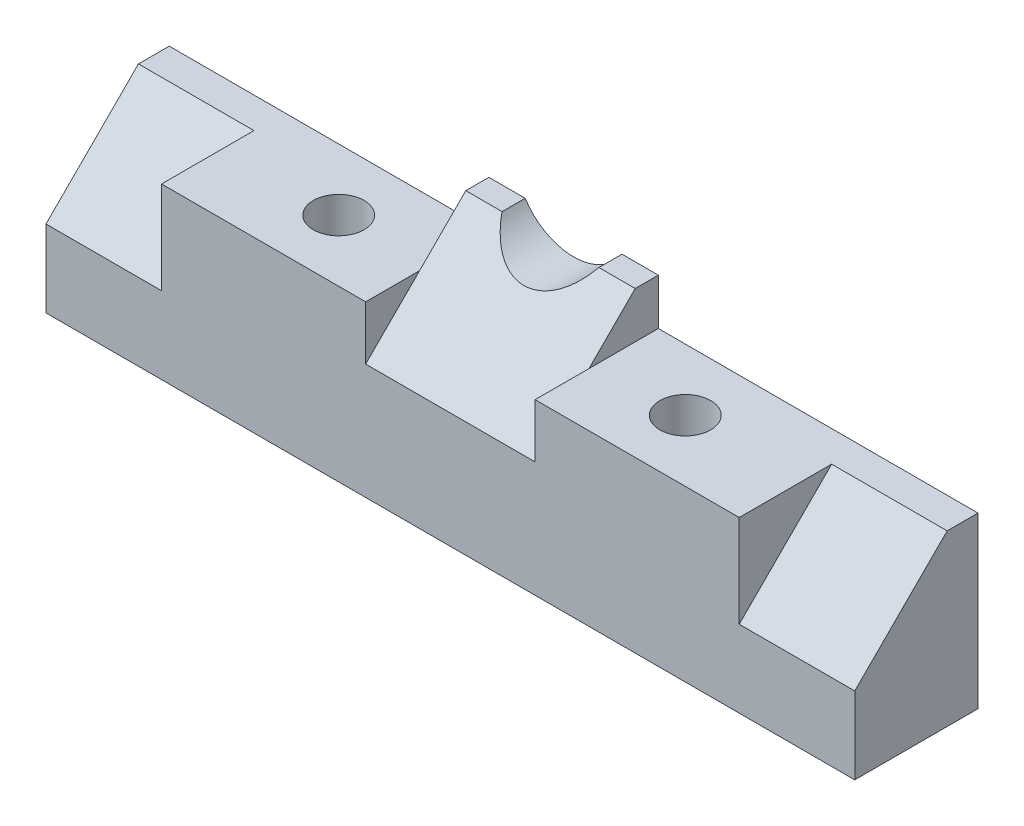
SolidWorks part; units mm, degrees
ref_plane "Alzado" through (0, 0, 0) normal (0, 0, 1) x (1, 0, 0)
ref_plane "Planta" through (0, 0, 0) normal (0, 1, 0) x (1, 0, 0)
ref_plane "Vista lateral" through (0, 0, 0) normal (1, 0, 0) x (0, 0, -1)
sketch "Croquis1" plane through (0, 0, 0) normal (0, 0, 1) x (1, 0, 0)
  line L1 (0, 0) -> (105, 0)
  line L2 (0, 0) -> (0, 22)
  line L3 (0, 22) -> (105, 22)
  line L4 (105, 0) -> (105, 22)
  dimension "D1" = 105
  dimension "D2" = 22
extrude "Saliente-Extruir1" add sketch "Croquis1" along normal blind 16
sketch "Croquis2" plane through (105, 0, 0) normal (1, 0, 0) x (0, 0, -1)
  line L2 (-16, 22) -> (0, 22) construction
  line L4 (-16, 0) -> (-16, 22) construction
  line L8 (-16, 10) -> (-16, 22)
  line L9 (-16, 22) -> (-4, 22)
  line L10 (-16, 10) -> (-4, 22)
extrude "Cortar-Extruir2" cut sketch "Croquis2" against normal blind 15
extrude "Cortar-Extruir3" cut sketch "Croquis2<2>" along normal blind 15 from surface starting at face at (0, 11, 8)
sketch "Croquis2<2>" plane through (105, 0, 0) normal (1, 0, 0) x (0, 0, -1) same geometry as "Croquis2"
sketch "Croquis3" plane through (0, 0, 16) normal (0, 0, 1) x (1, 0, 0)
  line L0 (52.5, 45.09) -> (52.5, -11.8197) construction
  line L1 (90, 22) -> (15, 22) construction
  line L2 (63.5, 15) -> (41.5, 15)
  line L3 (63.5, 15) -> (63.5, 29)
  line L4 (63.5, 29) -> (41.5, 29)
  line L5 (41.5, 15) -> (41.5, 29)
  line L6 (63.5, 15) -> (41.5, 29) construction
  line L7 (63.5, 29) -> (41.5, 15) construction
  line L9 (0, 0) -> (105, 0) construction
  point P2 (52.5, 22)
  dimension "D1" = 15
  dimension "D2" = 22
extrude "Cortar-Extruir4" cut sketch "Croquis3" against normal through all
sketch "Croquis4" plane through (41.5, 0, 0) normal (1, 0, 0) x (0, 0, -1)
  line L0 (-16, 15) -> (-3, 28)
  line L1 (-3, 28) -> (0, 28)
  line L2 (0, 28) -> (0, 15)
  line L3 (0, 15) -> (-16, 15)
  line L4 (-16, 22) -> (-16, 15) construction
  dimension "D1" = 3
  dimension "D2" = 45
extrude "Saliente-Extruir3" add sketch "Croquis4" along normal up to surface (22 mm away) up to face at (63.5, 18.5, 8)
sketch "Croquis5" plane through (0, 0, 0) normal (0, 0, -1) x (-1, 0, 0)
  line L3 (-52.5, 28) -> (-52.5, 32) construction
  line L4 (-63.5, 28) -> (-41.5, 28) construction
  circle A1 centre (-52.5, 32) radius 7.45
  dimension "D1" = 4
  dimension "D2" = 14.9
extrude "Cortar-Extruir6" cut sketch "Croquis5" against normal blind 15
sketch "Croquis7" plane through (0, 0, 0) normal (0, -1, 0) x (1, 0, 0)
  point P7 (30, 8)
  point P8 (75, 8)
hole_wizard "Refrentado para tornillo tapón con cabeza de clavija de M61" positions "Croquis8" profile "Croquis9" counterbore size "M6" standard "Autoliv NAM Metric" end condition through all
sketch "Croquis8" plane through (0, 0, 0) normal (0, -1, 0) x (-1, 0, 0)
  point P0 (-30, -8)
  point P3 (-75, -8)
sketch "Croquis9" plane through (30, 0, 8) normal (1, 0, 0) x (0, 0, -1)
  line L0 (0, 0) -> (0, 28)
  line L1 (0, 28) -> (3.3, 28)
  line L3 (3.3, 28) -> (3.3, 6)
  line L4 (5.5, 6) -> (3.3, 6)
  line L5 (5.5, 6) -> (5.5, 0.025)
  line L6 (5.5, 0.025) -> (5.525, 0)
  line L7 (5.525, 0) -> (0, 0)
  line L8 (-5.5, 0.025) -> (-5.525, 0) construction
  line L11 (0, -6.35) -> (0, 107.95) construction
  dimension "Diámetro de taladro hasta el siguiente" = 6.6
  dimension "Profundidad de taladro hasta el siguiente" = 28
  dimension "Diámetro de refrentado" = 11
  dimension "Profundidad de refrentado" = 6
  dimension "Diámetro de avellanado cercano" = 11.05
  dimension "Ángulo de avellanado cercano" = 90
